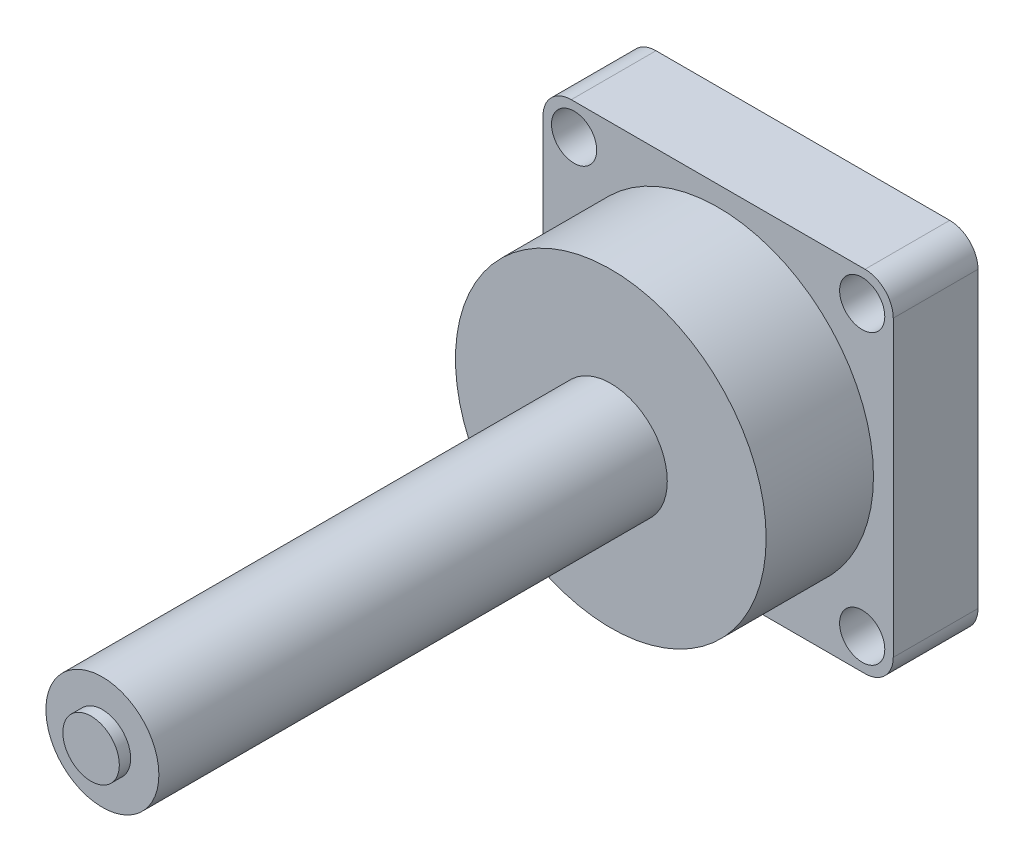
SolidWorks part; units mm, degrees
ref_plane "Front Plane" through (0, 0, 0) normal (0, 0, 1) x (1, 0, 0)
ref_plane "Top Plane" through (0, 0, 0) normal (0, 1, 0) x (1, 0, 0)
ref_plane "Right Plane" through (0, 0, 0) normal (1, 0, 0) x (0, 0, -1)
sketch "Sketch1" plane through (0, 0, 0) normal (0, 0, 1) x (1, 0, 0)
  line L0 (0, 75.4648) -> (0, -81.7288) construction
  line L1 (-26, -31) -> (26, -31)
  line L2 (-31, -26) -> (-31, 26)
  line L3 (-26, 31) -> (26, 31)
  line L4 (31, -26) -> (31, 26)
  line L5 (-31, -31) -> (31, 31) construction
  line L6 (-31, 31) -> (31, -31) construction
  line L7 (-63.5608, 0) -> (59.6509, 0) construction
  arc A0 (-31, -26) -> (-26, -31) centre (-26, -26) ccw
  arc A1 (31, -26) -> (26, -31) centre (26, -26) cw
  arc A2 (31, 26) -> (26, 31) centre (26, 26) ccw
  arc A3 (-26, 31) -> (-31, 26) centre (-26, 26) ccw
  circle A4 centre (25.5, 25.5) radius 4
  circle A5 centre (-25.5, 25.5) radius 4
  circle A6 centre (-25.5, -25.5) radius 4
  circle A7 centre (25.5, -25.5) radius 4
  circle A8 centre (0, 0) radius 27.5
  circle A9 centre (0, 0) radius 10
  circle A10 centre (0, 0) radius 5
  point P0 (0, 0)
  dimension "D2" = 5
  dimension "D4" = 8
  dimension "D5" = 55
  dimension "D6" = 20
  dimension "D7" = 10
  dimension "D1" = 62
  dimension "D3" = 25.5
extrude "Boss-Extrude1" add sketch "Sketch1" along normal blind 15 contours L3 A3 L2 A0 L1 A1 L4 A2 A8 A5 A4 A6 A7 region at (-28.9155, -28.9155, 0)
extrude "Boss-Extrude2" add sketch "Sketch1<3>" along normal blind 34 contours A8 region at (-26.7222, 0, 0)
sketch "Sketch1<3>" plane through (0, 0, 0) normal (0, 0, 1) x (1, 0, 0) same geometry as "Sketch1"
extrude "Boss-Extrude3" add sketch "Sketch1<4>" along normal blind 124 contours A9
sketch "Sketch1<4>" plane through (0, 0, 0) normal (0, 0, 1) x (1, 0, 0) same geometry as "Sketch1"
extrude "Boss-Extrude4" add sketch "Sketch1<5>" along normal blind 2 from surface contours A10 starting at face at (10, 0, 124)
sketch "Sketch1<5>" plane through (0, 0, 0) normal (0, 0, 1) x (1, 0, 0) same geometry as "Sketch1"
